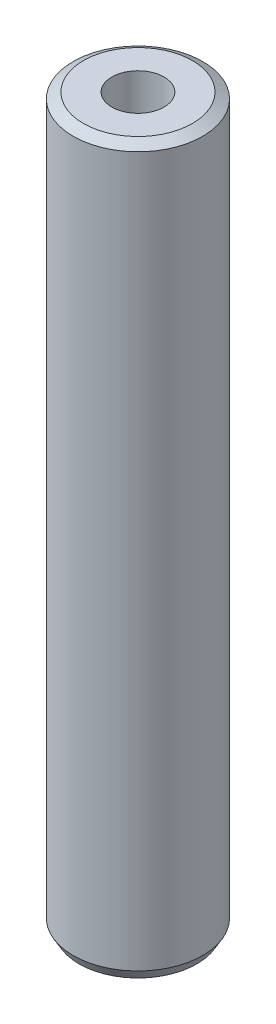
SolidWorks part; units mm, degrees
ref_plane "Front Plane" through (0, 0, 0) normal (0, 0, 1) x (1, 0, 0)
ref_plane "Top Plane" through (0, 0, 0) normal (0, 1, 0) x (1, 0, 0)
ref_plane "Right Plane" through (0, 0, 0) normal (1, 0, 0) x (0, 0, -1)
sketch "Sketch1" plane through (0, 0, 0) normal (0, 1, 0) x (1, 0, 0)
  circle A0 centre (0, 0) radius 37.5
  dimension "SHAFT_OD" = 75
extrude "Boss-Extrude1" add sketch "Sketch1" along normal blind 419.9832
sketch "Sketch2" plane through (0, 0, 0) normal (0, 1, 0) x (1, 0, 0)
  circle A0 centre (0, 0) radius 15.1142
  dimension "BORE_D" = 30.2283
extrude "Cut-Extrude1" cut sketch "Sketch2" along normal through all
chamfer "Chamfer1" distance 3.439 angle 60 2 edges at (0, 419.9832, 37.5) (0, 0, 37.5) first distance on face at (0, 419.9832, 37.5) first distance on face at (0, 0, 15.1142)
